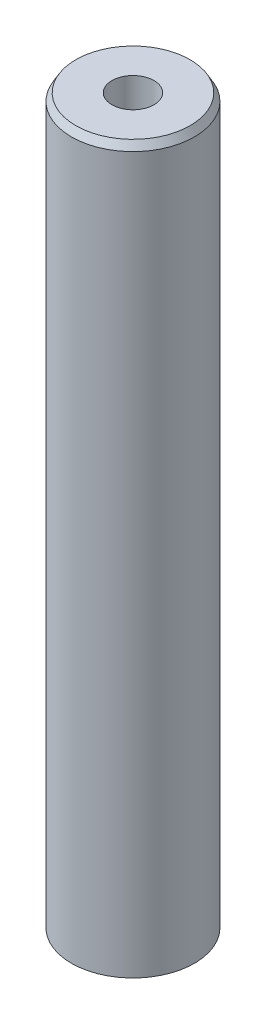
SolidWorks part; units mm, degrees
ref_plane "Front Plane" through (0, 0, 0) normal (0, 0, 1) x (1, 0, 0)
ref_plane "Top Plane" through (0, 0, 0) normal (0, 1, 0) x (1, 0, 0)
ref_plane "Right Plane" through (0, 0, 0) normal (1, 0, 0) x (0, 0, -1)
sketch "Sketch1" plane through (0, 0, 0) normal (0, 1, 0) x (1, 0, 0)
  circle A0 centre (0, 0) radius 25
  dimension "SHAFT_OD" = 50
extrude "Boss-Extrude1" add sketch "Sketch1" along normal blind 295.6271
sketch "Sketch2" plane through (0, 0, 0) normal (0, 1, 0) x (1, 0, 0)
  circle A0 centre (0, 0) radius 8.5393
  dimension "BORE_D" = 17.0787
extrude "Cut-Extrude1" cut sketch "Sketch2" along normal through all
chamfer "Chamfer1" distance 3.0743 angle 30 2 edges at (0, 295.6271, 25) (0, 0, 25) first distance on face at (0, 295.6271, 25) first distance on face at (0, 0, 8.5393)
